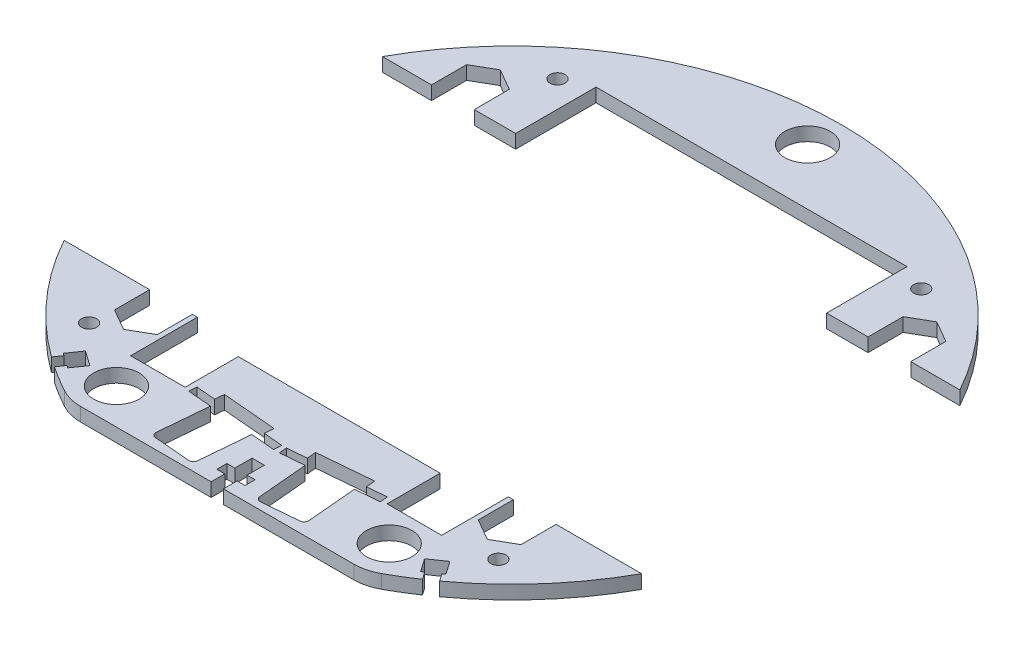
SolidWorks part; units mm, degrees
ref_plane "Front Plane" through (0, 0, 0) normal (0, 0, 1) x (1, 0, 0)
ref_plane "Top Plane" through (0, 0, 0) normal (0, 1, 0) x (1, 0, 0)
ref_plane "Right Plane" through (0, 0, 0) normal (1, 0, 0) x (0, 0, -1)
sketch "Sketch1" plane through (0, 0, 0) normal (0, 1, 0) x (1, 0, 0)
  line L0 (-30.03, -64.8129) -> (30.03, -64.8129)
  line L1 (0, -85) -> (0, 0) construction
  line L2 (0, -85) -> (32.4891, -64.8129) construction
  arc A0 (34.8348, -63.5829) -> (-34.8348, -63.5829) centre (0, 0) ccw
  circle A1 centre (0, -85) radius 38.25 construction
  arc A2 (30.03, -64.8129) -> (34.8348, -63.5829) centre (30.03, -54.8129) ccw
  arc A3 (-30.03, -64.8129) -> (-34.8348, -63.5829) centre (-30.03, -54.8129) cw
  dimension "D1" = 145
  dimension "D2" = 76.5
  dimension "D4" = 10
  dimension "D3" = 85
extrude "Boss-Extrude1" add sketch "Sketch1" along normal blind 3
sketch "Sketch2" plane through (0, 3, 0) normal (0, 1, 0) x (1, 0, 0)
  line L29 (-22.2, -49.6757) -> (-22.2, -32.5) construction
  line L30 (-22.2, -49.6757) -> (-22.2, -32.5) construction
  line L38 (-34.2, -49.6757) -> (-22.2, -49.6757) construction
  line L39 (-34.2, -49.6757) -> (-34.2, 49.6757) construction
  line L40 (-34.2, 49.6757) -> (-22.2, 49.6757) construction
  line L41 (-22.2, 32.5) -> (-22.2, 49.6757) construction
  line L47 (22.2, 32.5) -> (22.2, 49.6757) construction
  line L48 (34.2, 49.6757) -> (22.2, 49.6757) construction
  line L49 (34.2, -49.6757) -> (34.2, 49.6757) construction
  line L50 (34.2, -49.6757) -> (22.2, -49.6757) construction
  line L51 (22.2, -49.6757) -> (22.2, -32.5) construction
  line L52 (22.2, -49.6757) -> (22.2, -32.5) construction
  line L53 (-22.2, -49.6757) -> (-22.2, -38) construction
  line L54 (-22.2, -49.6757) -> (-22.2, -38)
  line L55 (-22.2, 44) -> (22.2, 44)
  line L62 (-34.2, -49.6757) -> (-22.2, -49.6757)
  line L63 (-34.2, -49.6757) -> (-34.2, 49.6757)
  line L64 (-34.2, 49.6757) -> (-22.2, 49.6757)
  line L65 (-22.2, 44) -> (-22.2, 49.6757)
  line L71 (22.2, 44) -> (22.2, 49.6757)
  line L72 (34.2, 49.6757) -> (22.2, 49.6757)
  line L73 (34.2, -49.6757) -> (34.2, 49.6757)
  line L74 (34.2, -49.6757) -> (22.2, -49.6757)
  line L75 (22.2, -49.6757) -> (22.2, -38) construction
  line L76 (22.2, -49.6757) -> (22.2, -38)
  line L77 (-22.2, -38) -> (22.2, -38)
  dimension "D1" = 38
  dimension "D2" = 44
extrude "Cut-Extrude1" cut sketch "Sketch2" against normal through all contours L54 L77 L76 L74 L73 L72 L71 L55 L65 L64 L63 L62 region at (0, 3, -1.8128)
sketch "Sketch3" plane through (0, 3, 0) normal (0, 1, 0) x (1, 0, 0)
  line L0 (-34.2, 35) -> (-34.2, -35)
  line L1 (-72.5, -35) -> (-34.2, -35)
  line L2 (-72.5, -35) -> (-72.5, 35)
  line L3 (-72.5, 35) -> (-34.2, 35)
  line L4 (72.5, -35) -> (72.5, 35)
  line L5 (-72.5, -35) -> (72.5, 35) construction
  line L6 (-72.5, 35) -> (72.5, -35) construction
  line L8 (34.2, 35) -> (34.2, -35)
  line L10 (34.2, 35) -> (72.5, 35)
  line L11 (34.2, -35) -> (72.5, -35)
  line L12 (-34.2, -49.6757) -> (-34.2, 49.6757) construction
  line L13 (34.2, -49.6757) -> (34.2, 49.6757) construction
  arc A0 (34.8348, -63.5829) -> (-34.8348, -63.5829) centre (0, 0) ccw construction
  point P0 (0, 0)
  dimension "D1" = 70
extrude "Cut-Extrude2" cut sketch "Sketch3" against normal through all
sketch "Sketch4" plane through (0, 3, 0) normal (0, 1, 0) x (1, 0, 0)
  line L0 (-21.0702, -50.0262) -> (-0.6482, -51.8129)
  line L1 (21.0702, -50.0262) -> (20.922, -48.3326)
  line L2 (0.6482, -51.8129) -> (0.5, -50.1193)
  line L3 (20.922, -48.3326) -> (0.5, -50.1193)
  line L4 (0, 0) -> (0, -64.8129) construction
  line L5 (-30.03, -64.8129) -> (30.03, -64.8129) construction
  line L6 (-20.922, -48.3326) -> (-0.5, -50.1193)
  line L7 (-0.6482, -51.8129) -> (-0.5, -50.1193)
  line L8 (-21.0702, -50.0262) -> (-20.922, -48.3326)
  line L14 (21.0702, -50.0262) -> (0.6482, -51.8129)
  dimension "D1" = 1.7
  dimension "D2" = 20.5
  dimension "D3" = 5
  dimension "D4" = 13
  dimension "D5" = 0.5
extrude "Cut-Extrude3" cut sketch "Sketch4" against normal through all
sketch "Sketch5" plane through (0, 3, 0) normal (0, 1, 0) x (1, 0, 0)
  line L0 (5.8782, -51.3553) -> (15.8401, -50.4837)
  line L1 (5.8782, -51.3553) -> (6.8369, -62.3134)
  line L2 (15.8401, -50.4837) -> (16.7988, -61.4419)
  line L3 (7.9203, -63.2225) -> (15.8898, -62.5252)
  line L4 (0.6482, -51.8129) -> (21.0702, -50.0262) construction
  line L5 (16.6882, -48.7031) -> (4.7338, -49.7489)
  line L6 (16.6882, -48.7031) -> (16.5139, -46.7107)
  line L7 (4.7338, -49.7489) -> (4.5595, -47.7565)
  line L8 (16.5139, -46.7107) -> (4.5595, -47.7565)
  line L9 (20.922, -48.3326) -> (0.5, -50.1193) construction
  line L10 (0, -38) -> (0, -64.8129) construction
  line L12 (-30.03, -64.8129) -> (30.03, -64.8129) construction
  line L13 (-16.5139, -46.7107) -> (-4.5595, -47.7565)
  line L14 (-4.7338, -49.7489) -> (-4.5595, -47.7565)
  line L15 (-16.6882, -48.7031) -> (-16.5139, -46.7107)
  line L16 (-16.6882, -48.7031) -> (-4.7338, -49.7489)
  line L17 (-7.9203, -63.2225) -> (-15.8898, -62.5252)
  line L18 (-15.8401, -50.4837) -> (-16.7988, -61.4419)
  line L19 (-5.8782, -51.3553) -> (-6.8369, -62.3134)
  line L20 (-5.8782, -51.3553) -> (-15.8401, -50.4837)
  line L21 (-22.2, -38) -> (22.2, -38) construction
  arc A0 (16.7988, -61.4419) -> (15.8898, -62.5252) centre (15.8027, -61.529) cw
  arc A1 (6.8369, -62.3134) -> (7.9203, -63.2225) centre (7.8331, -62.2263) ccw
  arc A2 (-6.8369, -62.3134) -> (-7.9203, -63.2225) centre (-7.8331, -62.2263) cw
  arc A3 (-16.7988, -61.4419) -> (-15.8898, -62.5252) centre (-15.8027, -61.529) ccw
  point P14 (10.711, -49.226)
  point P15 (10.711, -49.226)
  point P17 (10.8592, -50.9195)
  point P18 (10.8592, -50.9195)
  point P21 (16.886, -62.4381)
  point P24 (6.9241, -63.3096)
  point P40 (-6.9241, -63.3096)
  point P41 (-16.886, -62.4381)
  dimension "D5" = 1
  dimension "D1" = 12
  dimension "D2" = 10
  dimension "D3" = 12
  dimension "D4" = 2
extrude "Cut-Extrude4" cut sketch "Sketch5" against normal through all
sketch "Sketch6" plane through (0, 3, 0) normal (0, 1, 0) x (1, 0, 0)
  line L2 (-34.2, 49.6757) -> (34.2, 49.6757)
  line L3 (-34.2, 49.6757) -> (-34.2, 52.6757)
  line L4 (-34.2, 52.6757) -> (34.2, 52.6757)
  line L5 (34.2, 49.6757) -> (34.2, 52.6757)
  point P4 (34.2, 49.6757)
  dimension "D1" = 3
extrude "Cut-Extrude5" cut sketch "Sketch6" against normal through all body kept at (63.4921, 0, -35)
sketch "Sketch7" plane through (0, 3, 0) normal (0, 1, 0) x (1, 0, 0)
  circle A1 centre (-30, -57) radius 5
  circle A2 centre (-30, -57) radius 5
  circle A3 centre (30, -57) radius 5
  circle A4 centre (30, -57) radius 5
  dimension "D1" = 0
  dimension "D2" = 0
extrude "Cut-Extrude6" cut sketch "Sketch7" against normal through all
sketch "Sketch8" plane through (0, 3, 0) normal (0, 1, 0) x (1, 0, 0)
  line L10 (-52.7, 37.2865) -> (-52.7, 32.5)
  line L11 (-52.7, 32.5) -> (-43.3, 32.5)
  line L12 (-43.3, 32.5) -> (-43.3, 37.2865)
  line L13 (-43.3, 37.2865) -> (-43.3, 42.7135)
  line L14 (-43.3, 42.7135) -> (-48, 45.4271)
  line L15 (-48, 45.4271) -> (-52.7, 42.7135)
  line L16 (-52.7, 42.7135) -> (-52.7, 37.2865)
  line L17 (-52.7, 37.2865) -> (-52.7, 32.5)
  line L18 (-52.7, 32.5) -> (-43.3, 32.5)
  line L19 (-43.3, 32.5) -> (-43.3, 37.2865)
  line L20 (-43.3, 37.2865) -> (-43.3, 42.7135)
  line L21 (-43.3, 42.7135) -> (-48, 45.4271)
  line L22 (-48, 45.4271) -> (-52.7, 42.7135)
  line L23 (-52.7, 42.7135) -> (-52.7, 37.2865)
  line L24 (44.7, -32.5) -> (35.3, -32.5)
  line L25 (44.7, -37.2865) -> (44.7, -32.5)
  line L26 (44.7, -42.7135) -> (44.7, -37.2865)
  line L31 (40, -45.4271) -> (44.7, -42.7135)
  line L32 (35.3, -42.7135) -> (40, -45.4271)
  line L33 (35.3, -37.2865) -> (35.3, -42.7135)
  line L34 (35.3, -32.5) -> (35.3, -37.2865)
  line L35 (44.7, -32.5) -> (35.3, -32.5)
  line L36 (44.7, -37.2865) -> (44.7, -32.5)
  line L37 (44.7, -42.7135) -> (44.7, -37.2865)
  line L38 (40, -45.4271) -> (44.7, -42.7135)
  line L39 (35.3, -42.7135) -> (40, -45.4271)
  line L40 (35.3, -37.2865) -> (35.3, -42.7135)
  line L41 (35.3, -32.5) -> (35.3, -37.2865)
  line L42 (-35.3, -37.2865) -> (-35.3, -32.5)
  line L43 (-35.3, -32.5) -> (-44.7, -32.5)
  line L44 (-44.7, -32.5) -> (-44.7, -37.2865)
  line L45 (-44.7, -37.2865) -> (-44.7, -42.7135)
  line L46 (-44.7, -42.7135) -> (-40, -45.4271)
  line L47 (-40, -45.4271) -> (-35.3, -42.7135)
  line L48 (-35.3, -42.7135) -> (-35.3, -37.2865)
  line L49 (-35.3, -37.2865) -> (-35.3, -32.5)
  line L50 (-35.3, -32.5) -> (-44.7, -32.5)
  line L51 (-44.7, -32.5) -> (-44.7, -37.2865)
  line L52 (-44.7, -37.2865) -> (-44.7, -42.7135)
  line L53 (-44.7, -42.7135) -> (-40, -45.4271)
  line L54 (-40, -45.4271) -> (-35.3, -42.7135)
  line L55 (-35.3, -42.7135) -> (-35.3, -37.2865)
  line L56 (52.7, 32.5) -> (52.7, 37.2865)
  line L57 (52.7, 37.2865) -> (52.7, 42.7135)
  line L58 (52.7, 42.7135) -> (48, 45.4271)
  line L59 (48, 45.4271) -> (43.3, 42.7135)
  line L60 (43.3, 42.7135) -> (43.3, 37.2865)
  line L61 (43.3, 37.2865) -> (43.3, 32.5)
  line L62 (43.3, 32.5) -> (52.7, 32.5)
  line L63 (52.7, 32.5) -> (52.7, 37.2865)
  line L64 (52.7, 37.2865) -> (52.7, 42.7135)
  line L65 (52.7, 42.7135) -> (48, 45.4271)
  line L66 (48, 45.4271) -> (43.3, 42.7135)
  line L67 (43.3, 42.7135) -> (43.3, 37.2865)
  line L68 (43.3, 37.2865) -> (43.3, 32.5)
  line L69 (43.3, 32.5) -> (52.7, 32.5)
  dimension "D1" = 0
  dimension "D2" = 0
  dimension "D3" = 0
  dimension "D4" = 0
extrude "Cut-Extrude7" cut sketch "Sketch8" against normal through all
sketch "Sketch11" plane through (0, 3, 0) normal (0, 1, 0) x (1, 0, 0)
  line L0 (0, 0) -> (0, 65) construction
  circle A0 centre (0, 65) radius 5
  dimension "D2" = 10
  dimension "D1" = 65
extrude "Cut-Extrude10" cut sketch "Sketch11" against normal through all
sketch "Sketch12" plane through (0, 3, 0) normal (0, 1, 0) x (1, 0, 0)
  line L0 (-30.03, -64.8129) -> (30.03, -64.8129) construction
  line L1 (-1.35, -64.8129) -> (1.35, -64.8129)
  line L2 (-1.35, -64.8129) -> (-1.35, -61.8129)
  line L3 (-1.35, -55.8129) -> (1.35, -55.8129)
  line L4 (1.35, -64.8129) -> (1.35, -61.8129)
  line L5 (-1.35, -59.6129) -> (-3.1, -59.6129)
  line L6 (3.1, -59.6129) -> (1.35, -59.6129)
  line L7 (3.1, -59.6129) -> (3.1, -61.8129)
  line L8 (3.1, -61.8129) -> (1.35, -61.8129)
  line L9 (-3.1, -59.6129) -> (-3.1, -61.8129)
  line L10 (-1.35, -61.8129) -> (-3.1, -61.8129)
  line L11 (-1.35, -59.6129) -> (-1.35, -55.8129)
  line L12 (1.35, -59.6129) -> (1.35, -55.8129)
  point P14 (0, -64.8129)
  point P15 (0, -64.8129)
  dimension "D1" = 3
  dimension "D2" = 9
  dimension "D3" = 2.7
  dimension "D4" = 2.2
  dimension "D5" = 6.2
extrude "Cut-Extrude11" cut sketch "Sketch12" against normal through all
sketch "Sketch13" plane through (0, 3, 0) normal (0, 1, 0) x (1, 0, 0)
  line L0 (0, 0) -> (0, -22.8942) construction
  circle A0 centre (45, -48) radius 1.65
  circle A1 centre (-45, -48) radius 1.65
  circle A2 centre (40, 50) radius 1.65
  circle A3 centre (-40, 50) radius 1.65
  dimension "D3" = 3.3
  dimension "D1" = 48
  dimension "D2" = 45
  dimension "D4" = 40
  dimension "D5" = 50
extrude "Cut-Extrude12" cut sketch "Sketch13" against normal through all
sketch "Sketch14" plane through (0, 0, 0) normal (0, -1, 0) x (1, 0, 0)
  line L8 (-41.543, 56.9759) -> (-42.0754, 56.6031)
  line L9 (-42.0754, 56.6031) -> (-40.0679, 53.736)
  line L10 (-40.0679, 53.736) -> (-36.7913, 56.0303)
  line L11 (-36.7913, 56.0303) -> (-38.7988, 58.8974)
  line L12 (-38.7988, 58.8974) -> (-39.3313, 58.5245)
  line L13 (-39.3313, 58.5245) -> (-40.4784, 60.1629)
  line L14 (-40.4784, 60.1629) -> (-42.6901, 58.6142)
  line L15 (-42.6901, 58.6142) -> (-41.543, 56.9759)
  line L16 (-41.543, 56.9759) -> (-42.0754, 56.6031)
  line L17 (-42.0754, 56.6031) -> (-40.0679, 53.736)
  line L18 (-40.0679, 53.736) -> (-36.7913, 56.0303)
  line L19 (-36.7913, 56.0303) -> (-38.7988, 58.8974)
  line L20 (-38.7988, 58.8974) -> (-39.3313, 58.5245)
  line L21 (-39.3313, 58.5245) -> (-40.4784, 60.1629)
  line L22 (-40.4784, 60.1629) -> (-42.6901, 58.6142)
  line L23 (-42.6901, 58.6142) -> (-41.543, 56.9759)
  line L24 (41.543, 56.9759) -> (42.6901, 58.6142)
  line L25 (42.0754, 56.6031) -> (41.543, 56.9759)
  line L26 (40.0679, 53.736) -> (42.0754, 56.6031)
  line L27 (36.7913, 56.0303) -> (40.0679, 53.736)
  line L28 (38.7988, 58.8974) -> (36.7913, 56.0303)
  line L29 (39.3313, 58.5245) -> (38.7988, 58.8974)
  line L30 (40.4784, 60.1629) -> (39.3313, 58.5245)
  line L31 (42.6901, 58.6142) -> (40.4784, 60.1629)
  line L32 (41.543, 56.9759) -> (42.6901, 58.6142)
  line L33 (42.0754, 56.6031) -> (41.543, 56.9759)
  line L34 (40.0679, 53.736) -> (42.0754, 56.6031)
  line L35 (36.7913, 56.0303) -> (40.0679, 53.736)
  line L36 (38.7988, 58.8974) -> (36.7913, 56.0303)
  line L37 (39.3313, 58.5245) -> (38.7988, 58.8974)
  line L38 (40.4784, 60.1629) -> (39.3313, 58.5245)
  line L39 (42.6901, 58.6142) -> (40.4784, 60.1629)
  dimension "D1" = 0
  dimension "D2" = 0
extrude "Cut-Extrude13" cut sketch "Sketch14" against normal through all
equation "\"smallPulleyTeeth\"= 30"
equation "\"largePulleyTeeth\"= 30"
equation "\"eighthThick\"= 3.0mm"
equation "\"sixteenthThick\" = 1.7mm"
equation "\"quarterThick\"=6.0mm"
equation "\"OD\" = 145mm"
equation "\"puckAngle\" = 60.5deg"
equation "\"puckDiam\" = 76.5mm"
equation "\"axlePress\" = 5.9mm"
equation "\"press\" = 0.2mm"
equation "\"wheelClear\" = 0.3mm"
equation "\"10-32clear\" = 4.8mm"
equation "\"6-32clear\" = 3.3mm"
equation "\"8-32clear\" = 4.0mm"
equation "\"4-40clear\" = 3.0mm"
equation "\"wheelHeight\" = 22mm"
equation "\"wheelWell\" = 65mm"
equation "\"D1@Sketch1\"=\"OD\""
equation "\"D1@Boss-Extrude1\"=\"eighthThick\""
equation "\"D2@Sketch1\"=\"puckDiam\""
equation "\"puckDist\" = 85mm"
equation "\"scoopFillet\" = 5mm"
equation "\"10-32tap\" = 4.45mm"
equation "\"ledSmall\" = 3.1mm"
equation "\"ledLarge\" = 4.2mm"
equation "\"ledLength\" = 4.2mm"
equation "\"D3@Sketch1\"=\"puckDist\""
equation "\"4-40close\" = 2.7mm"
equation "\"4-40nutThick\" = 2.2mm"
equation "\"4-40nutWidth\" = 6.2mm"
equation "\"D3@Sketch12\"=\"4-40close\""
equation "\"D4@Sketch12\"=\"4-40nutThick\""
equation "\"D5@Sketch12\"=\"4-40nutWidth\""
equation "\"D3@Sketch13\"=\"6-32clear\""
equation "\"D1@Sketch6\"=\"eighthThick\""
